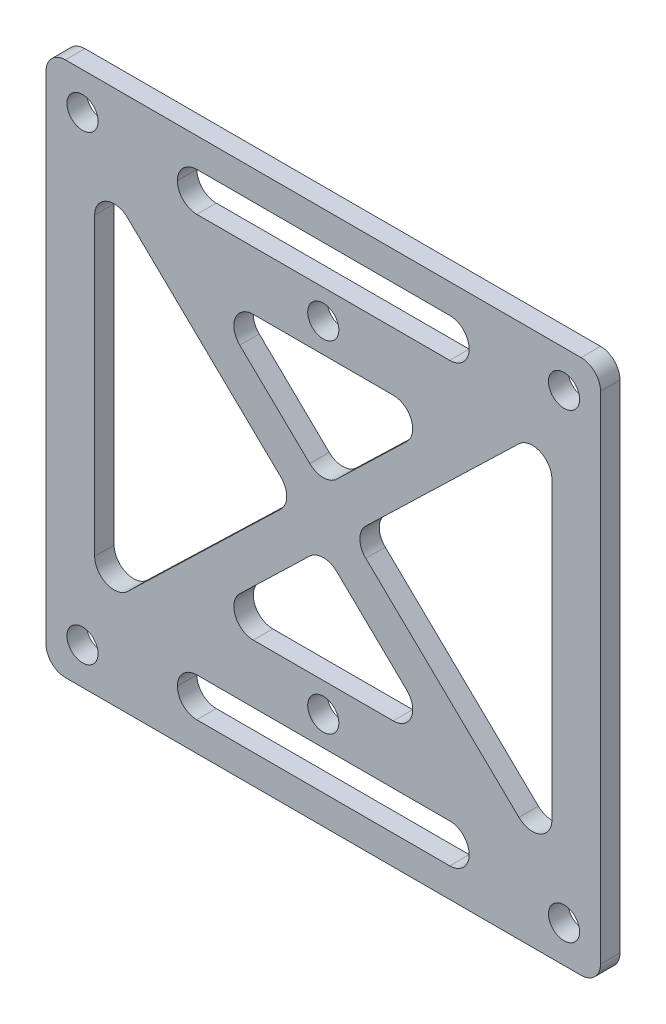
SolidWorks part; units mm, degrees
material "碳板"
ref_plane "前视基准面" through (0, 0, 0) normal (0, 0, 1) x (1, 0, 0)
ref_plane "上视基准面" through (0, 0, 0) normal (0, 1, 0) x (1, 0, 0)
ref_plane "右视基准面" through (0, 0, 0) normal (1, 0, 0) x (0, 0, -1)
sketch "草图1" plane through (0, 0, 0) normal (0, 0, 1) x (1, 0, 0)
  line L0 (0, 39.5379) -> (0, -39.8883) construction
  line L1 (-28.5, 27.5) -> (28.5, 27.5)
  line L2 (-28.5, 27.5) -> (-28.5, -27.5)
  line L3 (-28.5, -27.5) -> (28.5, -27.5)
  line L4 (28.5, 27.5) -> (28.5, -27.5)
  line L5 (-28.5, 27.5) -> (28.5, -27.5) construction
  line L6 (-28.5, -27.5) -> (28.5, 27.5) construction
  line L7 (-48.9406, 0) -> (49.5246, 0) construction
  line L8 (-2.8803, 0) -> (-23.5, 19.8962)
  line L9 (-23.5, 19.8962) -> (-23.5, -19.8962)
  line L10 (0, -2.7792) -> (-12.147, -14.5)
  line L11 (-12.147, -14.5) -> (0, -14.5)
  line L12 (-2.8803, 0) -> (-23.5, -19.8962)
  line L13 (-15, 24.5) -> (15, 24.5)
  line L14 (-15, 24.5) -> (-15, 20.5)
  line L15 (-15, 20.5) -> (15, 20.5)
  line L16 (15, 24.5) -> (15, 20.5)
  line L17 (-15, 24.5) -> (15, 20.5) construction
  line L18 (-15, 20.5) -> (15, 24.5) construction
  line L19 (12.147, -14.5) -> (0, -14.5)
  line L20 (0, -2.7792) -> (12.147, -14.5)
  line L21 (2.8803, 0) -> (23.5, 19.8962)
  line L22 (2.8803, 0) -> (23.5, -19.8962)
  line L23 (23.5, 19.8962) -> (23.5, -19.8962)
  line L24 (0, 2.7792) -> (12.147, 14.5)
  line L25 (0, 2.7792) -> (-12.147, 14.5)
  line L26 (-12.147, 14.5) -> (0, 14.5)
  line L27 (12.147, 14.5) -> (0, 14.5)
  line L28 (-15, -20.5) -> (15, -20.5)
  line L29 (15, -24.5) -> (15, -20.5)
  line L30 (-15, -24.5) -> (15, -24.5)
  line L31 (-15, -24.5) -> (-15, -20.5)
  circle A0 centre (24.75, 23.7) radius 1.6
  circle A1 centre (-24.75, 23.7) radius 1.6
  circle A2 centre (24.75, -23.7) radius 1.6
  circle A3 centre (-24.75, -23.7) radius 1.6
  circle A4 centre (0, 17.5) radius 1.6
  circle A5 centre (0, -17.5) radius 1.6
  point P0 (0, 0)
  point P28 (0, 22.5)
  point P34 (-23.5, 0)
  dimension "D3" = 3.2
  dimension "D6" = 3.2
  dimension "D7" = 35
  dimension "D1" = 57
  dimension "D2" = 55
  dimension "D4" = 47.4
  dimension "D5" = 49.5
  dimension "D8" = 10
  dimension "D9" = 5
  dimension "D10" = 2
  dimension "D11" = 4
  dimension "D12" = 3
  dimension "D13" = 3
  dimension "D14" = 30
  dimension "D15" = 4
extrude "凸台-拉伸1" add sketch "草图1" along normal blind 2
fillet "圆角1" radius 2 24 edges at (23.5, 19.8962, 1) (2.8803, 0, 1) (23.5, -19.8962, 1) (-15, 24.5, 1) (-15, 20.5, 1) (15, 20.5, 1) (15, 24.5, 1) (12.147, -14.5, 1) (0, -2.7792, 1) (-23.5, 19.8962, 1) (-23.5, -19.8962, 1) (-2.8803, 0, 1) (-12.147, -14.5, 1) (-28.5, -27.5, 1) (-28.5, 27.5, 1) (28.5, 27.5, 1) (28.5, -27.5, 1) (12.147, 14.5, 1) (0, 2.7792, 1) (-12.147, 14.5, 1) (15, -24.5, 1) (15, -20.5, 1) (-15, -24.5, 1) (-15, -20.5, 1)
